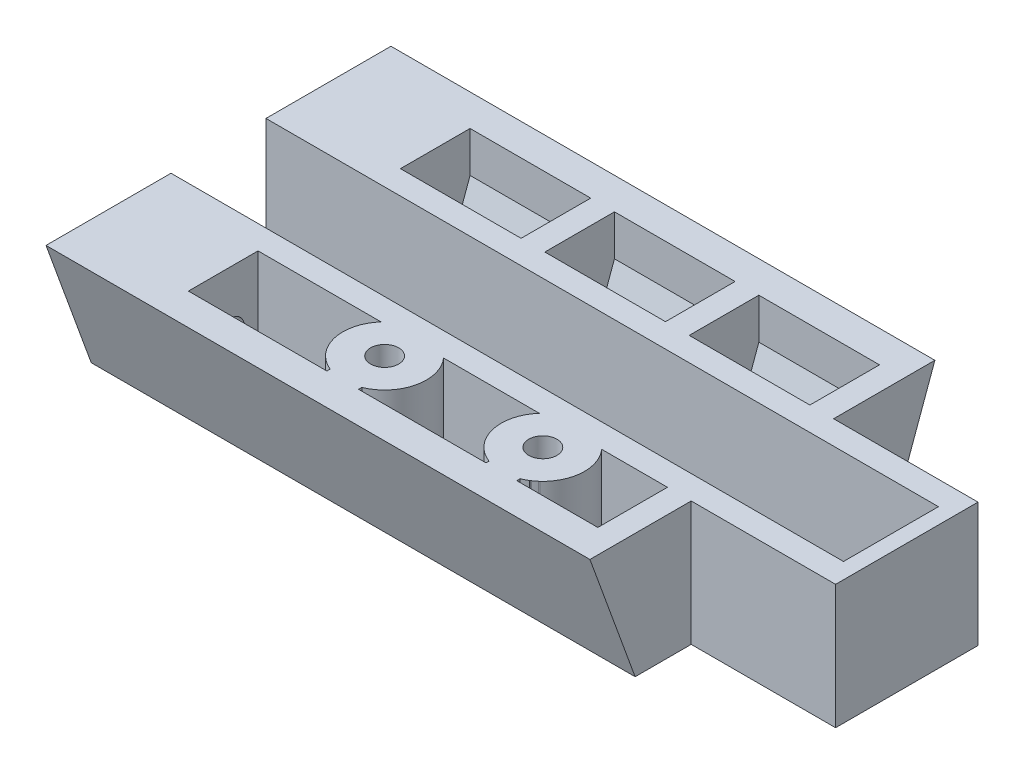
SolidWorks part; units mm, degrees
ref_plane "前视基准面" through (0, 0, 0) normal (0, 0, 1) x (1, 0, 0)
ref_plane "上视基准面" through (0, 0, 0) normal (0, 1, 0) x (1, 0, 0)
ref_plane "右视基准面" through (0, 0, 0) normal (1, 0, 0) x (0, 0, -1)
sketch "前视标记" plane through (0, 0, 0) normal (0, 0, 1) x (1, 0, 0)
  line L1 (0, 0) -> (0, 9.9695)
  line L3 (43.6563, 9.9695) -> (43.6563, 0)
  line L5 (55.245, 9.9695) -> (55.245, 0)
  line L7 (0, 0) -> (43.6563, 0)
  line L9 (43.6563, 0) -> (55.245, 0)
  line L11 (43.6563, 9.9695) -> (55.245, 9.9695)
  line L12 (0, 9.9695) -> (43.6563, 9.9695)
sketch "上视标记" plane through (0, 0, 0) normal (0, 1, 0) x (1, 0, 0)
  line L1 (0, 0) -> (0, -10.033)
  line L2 (24.3247, -23.1681) -> (30.9275, -23.1681)
  line L3 (0, 0) -> (43.6563, 0)
  line L4 (0, 0) -> (0, -27.686)
  line L5 (0, -27.686) -> (43.6563, -27.686)
  line L6 (43.6563, 0) -> (43.6563, -27.686)
  line L7 (55.245, -8.128) -> (43.6563, -8.128)
  line L8 (55.245, -8.128) -> (55.245, -19.558)
  line L9 (55.245, -19.558) -> (43.6563, -19.558)
  line L10 (43.6563, -8.128) -> (43.6563, -19.558)
  line L11 (52.07, -10.033) -> (0, -10.033)
  line L12 (52.07, -10.033) -> (52.07, -17.653)
  line L13 (52.07, -17.653) -> (0, -17.653)
  line L14 (0, -10.033) -> (0, -17.653)
  line L15 (53.975, -10.033) -> (52.07, -10.033)
  line L16 (53.975, -10.033) -> (53.975, -17.653)
  line L17 (53.975, -17.653) -> (52.07, -17.653)
  line L18 (52.07, -10.033) -> (52.07, -17.653)
  line L19 (8.89, -2.54) -> (18.5737, -2.54)
  line L20 (8.89, -2.54) -> (8.89, -8.128)
  line L21 (8.89, -8.128) -> (18.5737, -8.128)
  line L22 (18.5737, -2.54) -> (18.5737, -8.128)
  line L23 (20.4788, -8.128) -> (30.1625, -8.128)
  line L24 (20.4788, -8.128) -> (20.4788, -2.54)
  line L25 (20.4788, -2.54) -> (30.1625, -2.54)
  line L26 (30.1625, -8.128) -> (30.1625, -2.54)
  line L27 (32.0675, -2.54) -> (41.7513, -2.54)
  line L28 (32.0675, -2.54) -> (32.0675, -8.128)
  line L29 (32.0675, -8.128) -> (41.7513, -8.128)
  line L30 (41.7513, -2.54) -> (41.7513, -8.128)
  line L31 (8.89, -19.558) -> (18.7622, -19.558)
  line L32 (8.89, -19.558) -> (8.89, -25.146)
  line L33 (8.89, -25.146) -> (20.0025, -25.146)
  line L34 (20.0025, -24.8835) -> (20.0025, -25.146)
  line L35 (22.5425, -25.146) -> (32.7724, -25.146)
  line L36 (22.5425, -25.146) -> (22.5425, -24.8835)
  line L37 (22.5425, -19.558) -> (31.4709, -19.558)
  line L38 (32.7724, -25.146) -> (32.7724, -24.9041)
  line L39 (8.89, -23.1681) -> (18.2203, -23.1681)
  line L40 (41.7513, -19.558) -> (36.4741, -19.558)
  line L41 (41.7513, -19.558) -> (41.7513, -25.146)
  line L42 (41.7513, -25.146) -> (35.2425, -25.146)
  line L44 (37.0175, -23.1681) -> (41.7513, -23.1681)
  line L45 (35.2425, -24.8764) -> (35.2425, -25.146)
  circle A0 centre (21.2725, -21.7805) radius 1.1303
  circle A1 centre (21.2725, -21.7805) radius 3.3528
  circle A2 centre (33.9725, -21.7805) radius 1.1303
  circle A3 centre (33.9725, -21.7805) radius 3.3463
sketch "右视标记" plane through (0, 0, 0) normal (1, 0, 0) x (0, 0, -1)
  line L1 (-27.686, 9.9695) -> (-24.0574, 0)
  line L3 (-3.6286, 0) -> (0, 9.9695)
  line L4 (-27.686, 9.9695) -> (0, 9.9695)
  line L5 (-3.6286, 0) -> (-24.0574, 0)
  line L7 (-10.033, 9.9695) -> (-17.653, 9.9695)
  line L8 (-10.033, 9.9695) -> (-10.033, 1.27)
  line L9 (-10.033, 1.27) -> (-17.653, 1.27)
  line L10 (-17.653, 9.9695) -> (-17.653, 1.27)
  line L12 (-2.54, 6.7041) -> (-4.5179, 1.27)
  line L14 (-4.5179, 1.27) -> (-8.128, 1.27)
  line L16 (-2.54, 9.9695) -> (-2.54, 6.7041)
  line L18 (-8.128, 1.27) -> (-8.128, 9.9695)
  line L19 (0, 9.9695) -> (0, 0)
  line L20 (0, 0) -> (-3.6286, 0)
  line L21 (-8.128, 1.27) -> (-8.128, 0)
  circle A0 centre (-5.9055, 5.2586) radius 1.1303
  point P17 (-13.843, 9.9695)
ref_plane "中切面" through (0, 0, 13.843) normal (0, 0, 1) x (1, 0, 0)
sketch "草图4" plane through (0, 9.9695, 0) normal (0, 1, 0) x (1, 0, 0)
  line L0 (52.07, -10.033) -> (52.07, -17.653) construction
  line L1 (52.07, -17.653) -> (0, -17.653) construction
  line L2 (0, -10.033) -> (0, -17.653) construction
  line L3 (53.975, -10.033) -> (52.07, -10.033) construction
  line L4 (53.975, -10.033) -> (53.975, -17.653) construction
  line L5 (53.975, -17.653) -> (52.07, -17.653) construction
  line L6 (52.07, -10.033) -> (52.07, -17.653) construction
  line L7 (52.07, -10.033) -> (0, -10.033) construction
  line L8 (0, 0) -> (0, -10.033) construction
  line L9 (41.7513, -19.558) -> (36.4741, -19.558) construction
  line L10 (41.7513, -19.558) -> (41.7513, -25.146) construction
  line L11 (41.7513, -25.146) -> (35.2425, -25.146) construction
  line L12 (35.2425, -24.8764) -> (35.2425, -25.146) construction
  line L13 (8.89, -23.1681) -> (18.2203, -23.1681) construction
  line L14 (22.5425, -19.558) -> (31.4709, -19.558) construction
  line L15 (8.89, -19.558) -> (18.7622, -19.558) construction
  line L16 (8.89, -19.558) -> (8.89, -25.146) construction
  line L17 (8.89, -25.146) -> (20.0025, -25.146) construction
  line L18 (20.0025, -24.8835) -> (20.0025, -25.146) construction
  line L19 (24.3247, -23.1681) -> (30.9275, -23.1681) construction
  line L20 (37.0175, -23.1681) -> (41.7513, -23.1681) construction
  line L21 (32.7724, -25.146) -> (32.7724, -24.9041) construction
  line L22 (22.5425, -25.146) -> (32.7724, -25.146) construction
  line L23 (22.5425, -25.146) -> (22.5425, -24.8835) construction
  line L24 (55.245, -8.128) -> (43.6563, -8.128) construction
  line L25 (43.6563, -8.128) -> (43.6563, -19.558) construction
  line L26 (55.245, -19.558) -> (43.6563, -19.558) construction
  line L27 (55.245, -8.128) -> (55.245, -19.558) construction
  line L28 (0, 0) -> (43.6563, 0) construction
  line L29 (43.6563, 0) -> (43.6563, -27.686) construction
  line L30 (0, -27.686) -> (43.6563, -27.686) construction
  line L31 (0, 0) -> (0, -27.686) construction
  line L32 (20.4788, -8.128) -> (30.1625, -8.128) construction
  line L33 (30.1625, -8.128) -> (30.1625, -2.54) construction
  line L34 (20.4788, -2.54) -> (30.1625, -2.54) construction
  line L35 (20.4788, -8.128) -> (20.4788, -2.54) construction
  line L36 (8.89, -2.54) -> (18.5737, -2.54) construction
  line L37 (18.5737, -2.54) -> (18.5737, -8.128) construction
  line L38 (8.89, -8.128) -> (18.5737, -8.128) construction
  line L39 (8.89, -2.54) -> (8.89, -8.128) construction
  line L40 (32.0675, -2.54) -> (41.7513, -2.54) construction
  line L41 (41.7513, -2.54) -> (41.7513, -8.128) construction
  line L42 (32.0675, -8.128) -> (41.7513, -8.128) construction
  line L43 (32.0675, -2.54) -> (32.0675, -8.128) construction
  line L44 (52.07, -10.033) -> (52.07, -17.653)
  line L45 (52.07, -17.653) -> (0, -17.653)
  line L46 (0, -10.033) -> (0, -17.653)
  line L47 (53.975, -10.033) -> (52.07, -10.033)
  line L48 (53.975, -10.033) -> (53.975, -17.653)
  line L49 (53.975, -17.653) -> (52.07, -17.653)
  line L50 (52.07, -10.033) -> (52.07, -17.653)
  line L51 (52.07, -10.033) -> (0, -10.033)
  line L52 (0, 0) -> (0, -10.033)
  line L53 (41.7513, -19.558) -> (36.4741, -19.558)
  line L54 (41.7513, -19.558) -> (41.7513, -25.146)
  line L55 (41.7513, -25.146) -> (35.2425, -25.146)
  line L56 (35.2425, -24.8764) -> (35.2425, -25.146)
  line L57 (8.89, -23.1681) -> (18.2203, -23.1681)
  line L58 (22.5425, -19.558) -> (31.4709, -19.558)
  line L59 (8.89, -19.558) -> (18.7622, -19.558)
  line L60 (8.89, -19.558) -> (8.89, -25.146)
  line L61 (8.89, -25.146) -> (20.0025, -25.146)
  line L62 (20.0025, -24.8835) -> (20.0025, -25.146)
  line L63 (24.3247, -23.1681) -> (30.9275, -23.1681)
  line L64 (37.0175, -23.1681) -> (41.7513, -23.1681)
  line L65 (32.7724, -25.146) -> (32.7724, -24.9041)
  line L66 (22.5425, -25.146) -> (32.7724, -25.146)
  line L67 (22.5425, -25.146) -> (22.5425, -24.8835)
  line L68 (55.245, -8.128) -> (43.6563, -8.128)
  line L69 (43.6563, -8.128) -> (43.6563, -19.558)
  line L70 (55.245, -19.558) -> (43.6563, -19.558)
  line L71 (55.245, -8.128) -> (55.245, -19.558)
  line L72 (0, 0) -> (43.6563, 0)
  line L73 (43.6563, 0) -> (43.6563, -27.686)
  line L74 (0, -27.686) -> (43.6563, -27.686)
  line L75 (0, 0) -> (0, -27.686)
  line L76 (20.4788, -8.128) -> (30.1625, -8.128)
  line L77 (30.1625, -8.128) -> (30.1625, -2.54)
  line L78 (20.4788, -2.54) -> (30.1625, -2.54)
  line L79 (20.4788, -8.128) -> (20.4788, -2.54)
  line L80 (8.89, -2.54) -> (18.5737, -2.54)
  line L81 (18.5737, -2.54) -> (18.5737, -8.128)
  line L82 (8.89, -8.128) -> (18.5737, -8.128)
  line L83 (8.89, -2.54) -> (8.89, -8.128)
  line L84 (32.0675, -2.54) -> (41.7513, -2.54)
  line L85 (41.7513, -2.54) -> (41.7513, -8.128)
  line L86 (32.0675, -8.128) -> (41.7513, -8.128)
  line L87 (32.0675, -2.54) -> (32.0675, -8.128)
  circle A0 centre (33.9725, -21.7805) radius 3.3463 construction
  circle A1 centre (21.2725, -21.7805) radius 3.3528 construction
  circle A2 centre (21.2725, -21.7805) radius 1.1303 construction
  circle A3 centre (33.9725, -21.7805) radius 1.1303 construction
  circle A4 centre (33.9725, -21.7805) radius 3.3463
  circle A5 centre (21.2725, -21.7805) radius 3.3528
  circle A6 centre (21.2725, -21.7805) radius 1.1303
  circle A7 centre (33.9725, -21.7805) radius 1.1303
  line M100 (36.2214, -24.2672) -> (32.7724, -24.0284)
  line M101 (32.7724, -24.0284) -> (35.7587, -24.6179)
  line M102 (35.7587, -24.6179) -> (36.2214, -24.2672)
extrude "主体" add sketch "上视标记" along normal up to vertex (9.9695 mm away) contours L6 L13 L4 L5 A3 L40 L41 L42 L45 L38 L35 L36 A1 L34 L33 L32 L31 L37 | A1 L31 L32 L39 | A1 L39 L32 L33 L34 | A1 A0 | A3 L37 A1 L2 | A3 L2 A1 L36 L35 L38 | A3 A2 | A2 | A3 L44 L41 L40 | A3 L45 L42 L41 L44 | L16 L17 L13 L6 L9 L8 L7 L11 L15 | L17 L16 L15 L12 | L13 L10 L11 L4 | L11 L6 L3 L1 L19 L22 L21 L20 L26 L23 L24 L25 L27 L30 L29 L28 | L30 L27 L28 L29 | L23 L26 L25 L24 | L22 L19 L20 L21 | A0 region at (19.7714, 0, 4.8295) region at (21.8281, 0, 13.843) region at (21.8281, 0, 18.1009) region at (43.819, 0, 9.0805) region at (53.0225, 0, 13.843) region at (27.626, 0, 21.3158) region at (27.6323, 0, 24.2393) region at (23.5318, 0, 24.1278) region at (30.7571, 0, 21.2965) region at (13.978, 0, 24.1901) region at (39.4292, 0, 21.3304) region at (38.9465, 0, 24.2174) region at (13.5079, 0, 21.3467) region at (13.7319, 0, 5.334) region at (25.3206, 0, 5.334) region at (36.9094, 0, 5.334) region at (21.2725, 0, 21.7805) region at (33.9725, 0, 21.7805) up to point (0, 9.9695, 17.653)
extrude "切方块" cut sketch "草图4" against normal up to vertex (8.6995 mm away) contours L80 L83 L82 L81 | L79 L76 L77 L78 | L84 L87 L86 L85 | L49 L48 L47 L44 | L69 L51 L46 L45 | A5 L59 L60 L57 | A5 L57 L60 L61 L62 | A5 L63 A4 L58 | A5 L67 L66 L65 A4 L63 | A4 L56 L55 L54 L64 M102 M101 M100 | A4 L64 L54 L53 region at (53.0225, 9.9695, 13.843) region at (21.8281, 9.9695, 13.843) region at (39.4292, 9.9695, 21.3304) region at (38.9466, 9.9695, 24.2174) region at (27.626, 9.9695, 21.3158) region at (27.6323, 9.9695, 24.2393) region at (13.5079, 9.9695, 21.3467) region at (13.978, 9.9695, 24.1901) region at (25.3206, 9.9695, 5.334) region at (13.7319, 9.9695, 5.334) region at (36.9094, 9.9695, 5.334) up to point (0, 1.27, 17.653)
extrude "拉伸9" cut sketch "右视标记" along normal through all contours L20 L19 L3 region at (0, 3.3232, 1.2095)
extrude "拉伸10" add sketch "右视标记<6>" along normal up to surface (43.6563 mm away) contours L14 L21 L5 L3 L4 L16 L12 region at (0, 4.4243, 3.3153) up to face at (43.6563, 4.9847, 4.9712)
sketch "右视标记<6>" plane through (0, 0, 0) normal (1, 0, 0) x (0, 0, -1) same geometry as "右视标记"
extrude "拉伸11" cut sketch "右视标记<7>" along normal up to next contours A0 region at (0, 5.2586, 5.9055)
sketch "右视标记<7>" plane through (0, 0, 0) normal (1, 0, 0) x (0, 0, -1) same geometry as "右视标记"
mirror "镜向2" about plane through (0, 0, 13.843) normal (0, 0, 1) of "拉伸9", "拉伸10", "拉伸11"
extrude "拉伸12" cut sketch "上视标记<5>" along normal through all contours A0 | A2 region at (21.2725, 0, 21.7805) region at (33.9725, 0, 21.7805)
sketch "上视标记<5>" plane through (0, 0, 0) normal (0, 1, 0) x (1, 0, 0) same geometry as "上视标记"
